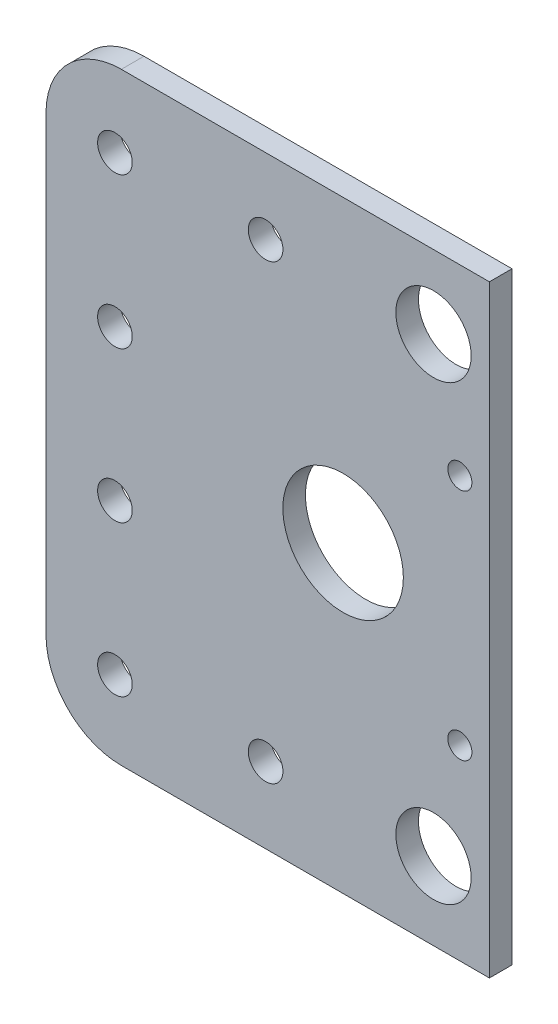
SolidWorks part; units mm, degrees
ref_plane "Front Plane" through (0, 0, 0) normal (0, 0, 1) x (1, 0, 0)
ref_plane "Top Plane" through (0, 0, 0) normal (0, 1, 0) x (1, 0, 0)
ref_plane "Right Plane" through (0, 0, 0) normal (1, 0, 0) x (0, 0, -1)
sketch "Sketch1" plane through (0, 0, 0) normal (0, 0, 1) x (1, 0, 0)
  line L0 (157.9607, -71.8662) -> (165.3807, -71.8662)
  line L1 (116.5258, -71.8662) -> (157.9607, -71.8662)
  line L2 (106.5258, -81.8662) -> (106.5258, -141.8968)
  line L3 (116.5258, -151.8968) -> (157.9607, -151.8968)
  line L4 (165.3807, -71.8662) -> (165.3807, -151.8968)
  line L5 (145.9607, -111.5917) -> (157.9607, -111.5917) construction
  line L6 (157.9607, -111.5917) -> (157.9607, -81.5917) construction
  line L7 (157.9607, -111.5917) -> (157.9607, -141.5917) construction
  line L8 (165.3807, -151.8968) -> (157.9607, -151.8968)
  circle A0 centre (115.6746, -101.8662) radius 2.3
  circle A1 centre (115.6746, -121.8662) radius 2.3
  circle A2 centre (135.6746, -141.8662) radius 2.3
  circle A3 centre (135.6746, -81.8662) radius 2.3
  circle A4 centre (115.6746, -81.8662) radius 2.3
  circle A5 centre (115.6746, -141.8662) radius 2.3
  circle A6 centre (161.4607, -96.1142) radius 1.6
  circle A7 centre (161.4607, -127.1142) radius 1.6
  circle A10 centre (145.9607, -111.5917) radius 8
  arc A13 (106.5258, -141.8968) -> (116.5258, -151.8968) centre (116.5258, -141.8968) ccw
  arc A14 (116.5258, -71.8662) -> (106.5258, -81.8662) centre (116.5258, -81.8662) ccw
  circle A15 centre (157.9607, -81.5917) radius 5
  circle A16 centre (157.9607, -141.5917) radius 5
  point P47 (106.5258, -71.8662)
  dimension "D4" = 12
  dimension "D2" = 30
  dimension "D3" = 30
extrude "Boss-Extrude1" add sketch "Sketch1" along normal blind 3
